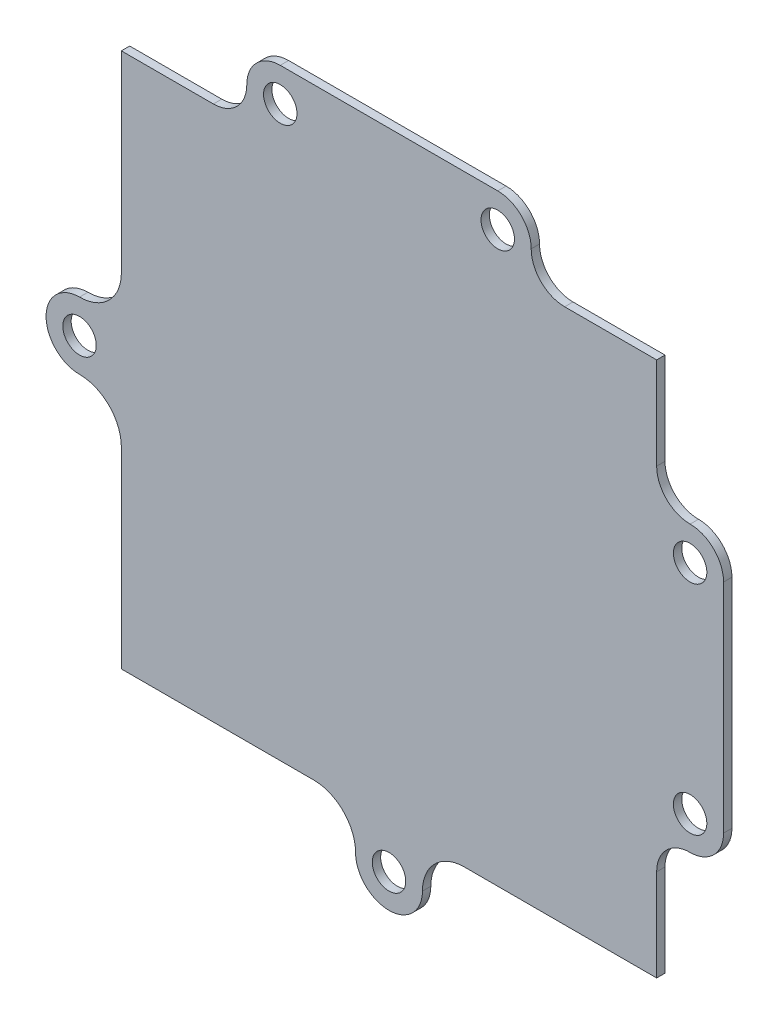
SolidWorks part; units mm, degrees
ref_plane "Top Plane" through (0, 0, 0) normal (0, 0, 1) x (1, 0, 0)
ref_plane "Right Plane" through (0, 0, 0) normal (0, 1, 0) x (1, 0, 0)
ref_plane "Front Plane" through (0, 0, 0) normal (1, 0, 0) x (0, 0, -1)
sketch "Sketch1" plane through (0, 0, 0) normal (0, 0, 1) x (1, 0, 0)
  line L44 (40, -13) -> (40, -9) construction
  line L47 (28, -28) -> (-28, -28) construction
  line L48 (-28, -28) -> (-28, 28) construction
  line L49 (-28, 28) -> (-9, 28) construction
  line L52 (-21, 32) -> (-32, 32) construction
  line L53 (-32, 32) -> (-32, 9) construction
  line L54 (-32, -9) -> (-32, -32) construction
  line L55 (-32, -32) -> (-9, -32) construction
  line L56 (9, -32) -> (32, -32) construction
  line L57 (32, -32) -> (32, -21) construction
  line L60 (32, 21) -> (32, 32) construction
  line L61 (32, 32) -> (21, 32) construction
  line L62 (13, 40) -> (9, 40) construction
  line L65 (28, 28) -> (28, 9) construction
  line L66 (40, -13) -> (40, 13)
  line L69 (28, -28) -> (-28, -28)
  line L70 (-28, -28) -> (-28, 28)
  line L71 (-28, 28) -> (28, 28)
  line L74 (-21, 32) -> (-32, 32)
  line L75 (-32, 32) -> (-32, 9)
  line L76 (-32, -9) -> (-32, -32)
  line L77 (-32, -32) -> (-9, -32)
  line L78 (9, -32) -> (32, -32)
  line L79 (32, -32) -> (32, -21)
  line L82 (32, 21) -> (32, 32)
  line L83 (32, 32) -> (21, 32)
  line L84 (13, 40) -> (-13, 40)
  line L87 (28, 28) -> (28, -28)
  arc A40 (36, -17) -> (40, -13) centre (36, -13) ccw construction
  arc A41 (-13, 40) -> (-17, 36) centre (-13, 36) ccw construction
  arc A42 (-21, 32) -> (-17, 36) centre (-21, 36) ccw construction
  arc A43 (-37, 4) -> (-32, 9) centre (-37, 9) ccw construction
  arc A44 (-37, 4) -> (-37, -4) centre (-37, 0) ccw construction
  arc A45 (-32, -9) -> (-37, -4) centre (-37, -9) ccw construction
  arc A46 (-4, -37) -> (-9, -32) centre (-9, -37) ccw construction
  arc A47 (-4, -37) -> (4, -37) centre (0, -37) ccw construction
  arc A48 (9, -32) -> (4, -37) centre (9, -37) ccw construction
  arc A49 (36, -17) -> (32, -21) centre (36, -21) ccw construction
  arc A50 (40, 13) -> (36, 17) centre (36, 13) ccw construction
  arc A51 (32, 21) -> (36, 17) centre (36, 21) ccw construction
  arc A52 (17, 36) -> (21, 32) centre (21, 36) ccw construction
  arc A53 (17, 36) -> (13, 40) centre (13, 36) ccw construction
  arc A54 (36, -17) -> (40, -13) centre (36, -13) ccw
  arc A55 (-13, 40) -> (-17, 36) centre (-13, 36) ccw
  arc A56 (-21, 32) -> (-17, 36) centre (-21, 36) ccw
  arc A57 (-37, 4) -> (-32, 9) centre (-37, 9) ccw
  arc A58 (-37, 4) -> (-37, -4) centre (-37, 0) ccw
  arc A59 (-32, -9) -> (-37, -4) centre (-37, -9) ccw
  arc A60 (-4, -37) -> (-9, -32) centre (-9, -37) ccw
  arc A61 (-4, -37) -> (4, -37) centre (0, -37) ccw
  arc A62 (9, -32) -> (4, -37) centre (9, -37) ccw
  arc A63 (36, -17) -> (32, -21) centre (36, -21) ccw
  arc A64 (40, 13) -> (36, 17) centre (36, 13) ccw
  arc A65 (32, 21) -> (36, 17) centre (36, 21) ccw
  arc A66 (17, 36) -> (21, 32) centre (21, 36) ccw
  arc A67 (17, 36) -> (13, 40) centre (13, 36) ccw
  circle A68 centre (-37, 0) radius 2 construction
  circle A69 centre (-13, 36) radius 2 construction
  circle A70 centre (0, -37) radius 2 construction
  circle A71 centre (36, -13) radius 2 construction
  circle A72 centre (36, 13) radius 2 construction
  circle A73 centre (13, 36) radius 2 construction
  circle A74 centre (-37, 0) radius 2
  circle A75 centre (-13, 36) radius 2
  circle A76 centre (0, -37) radius 2
  circle A77 centre (36, -13) radius 2
  circle A78 centre (36, 13) radius 2
  circle A79 centre (13, 36) radius 2
extrude "Boss-Extrude1" add sketch "Sketch1" along normal blind 1
chamfer "Chamfer1" [suppressed] distance 2 angle 45
ref_plane "Plane1" through (0, 0, 0.5) normal (0, 0, 1) x (1, 0, 0)
sketch "Sketch2" plane through (0, 0, 0.5) normal (0, 0, 1) x (1, 0, 0)
  line L0 (20, 28) -> (28, 20)
  line L1 (28, 20) -> (28, 28)
  line L2 (28, 28) -> (20, 28)
  line L3 (24, 28) -> (26, 26) construction
  line L4 (26, 26) -> (28, 24) construction
  line L6 (24, 24) -> (26, 26) construction
  circle A0 centre (26, 26) radius 1.25
  dimension "D1" = 8
  dimension "D2" = 2.5
extrude "Boss-Extrude2" [suppressed] add sketch "Sketch2" along normal mid plane 1
ref_axis "Axis1" [suppressed] through (0, 0, 5.25) along (0, 0, -1)
pattern_circular "CirPattern1" [suppressed] count 4 every 90 about axis through (0, 0, 5.25) along (0, 0, -1) of bodies 105
sketch "Sketch3" plane through (0, 0, 1) normal (0, 0, 1) x (1, 0, 0)
  line L0 (-28, 28) -> (-28, -28) construction
  line L1 (-28, -28) -> (28, -28) construction
  line L2 (28, -28) -> (28, 28) construction
  line L3 (28, 28) -> (-28, 28) construction
  line L4 (-28, 28) -> (-28, -28)
  line L5 (-28, -28) -> (28, -28)
  line L6 (28, -28) -> (28, 28)
  line L7 (28, 28) -> (-28, 28)
extrude "Boss-Extrude3" add sketch "Sketch3" against normal up to surface (1 mm away) up to face at (3.1696, 3.1696, 0)
